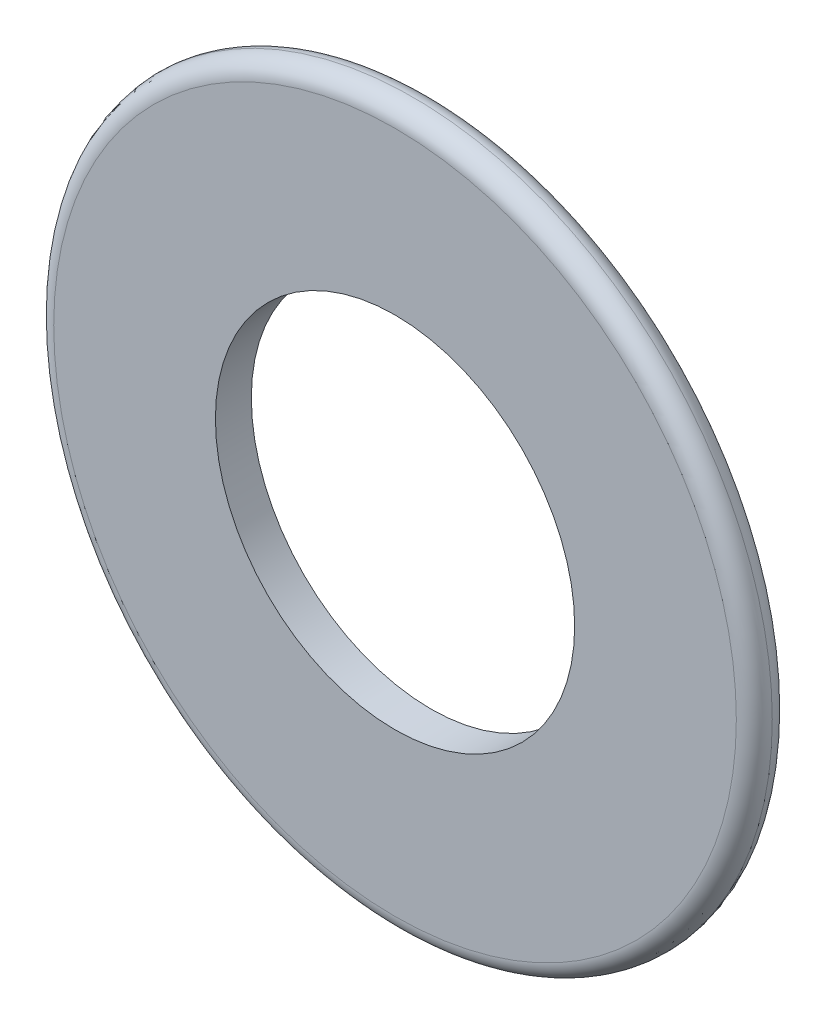
SolidWorks part; units mm, degrees
ref_plane "Front Plane" through (0, 0, 0) normal (0, 0, 1) x (1, 0, 0)
ref_plane "Top Plane" through (0, 0, 0) normal (0, 1, 0) x (1, 0, 0)
ref_plane "Right Plane" through (0, 0, 0) normal (1, 0, 0) x (0, 0, -1)
sketch "Sketch1" plane through (0, 0, 0) normal (0, 0, 1) x (1, 0, 0)
  circle A0 centre (0, 0) radius 5
  circle A1 centre (0, 0) radius 10
  dimension "D1" = 10
  dimension "D2" = 20
extrude "Boss-Extrude1" add sketch "Sketch1" along normal blind 1
fillet "Fillet1" radius 0.5 2 edges at (10, 0, 0) (10, 0, 1)
